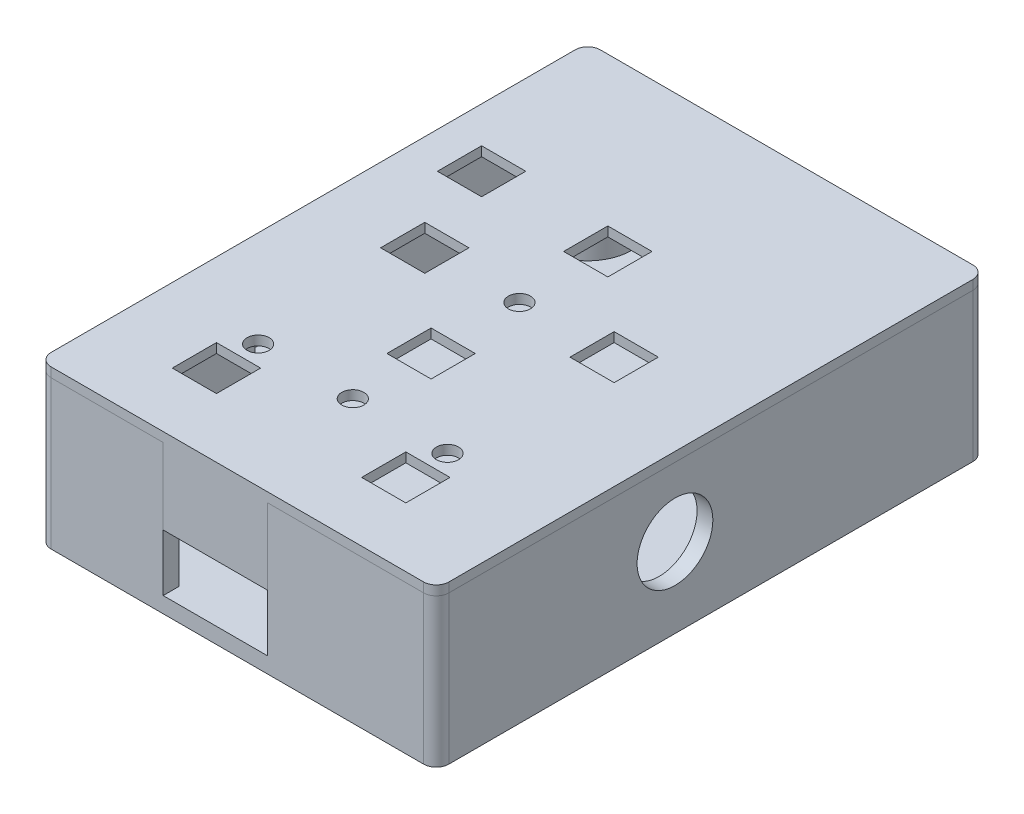
SolidWorks part; units mm, degrees
ref_plane "前视基准面" through (0, 0, 0) normal (0, 0, 1) x (1, 0, 0)
ref_plane "上视基准面" through (0, 0, 0) normal (0, 1, 0) x (1, 0, 0)
ref_plane "右视基准面" through (0, 0, 0) normal (1, 0, 0) x (0, 0, -1)
sketch "草图1" plane through (0, 0, 0) normal (0, 1, 0) x (1, 0, 0)
  line L0 (-11.76, -41) -> (-11.76, -43.5)
  line L1 (-26, 38) -> (26, 38) construction
  line L2 (-26, 38) -> (-26, -38) construction
  line L3 (-26, -38) -> (26, -38) construction
  line L4 (26, 38) -> (26, -38) construction
  line L5 (-26, 38) -> (26, -38) construction
  line L6 (-26, -38) -> (26, 38) construction
  line L7 (-29, 41) -> (29, 41)
  line L8 (-29, 41) -> (-29, -41)
  line L9 (-29, -41) -> (29, -41)
  line L10 (29, 41) -> (29, -41)
  line L11 (-29, 41) -> (29, -41) construction
  line L12 (-29, -41) -> (29, 41) construction
  line L13 (-29.5, 43.5) -> (29.5, 43.5)
  line L14 (-31.5, 41.5) -> (-31.5, -41.5)
  line L15 (-29.5, -43.5) -> (29.5, -43.5)
  line L16 (31.5, 41.5) -> (31.5, -41.5)
  line L17 (-31.5, 43.5) -> (31.5, -43.5) construction
  line L18 (-31.5, -43.5) -> (31.5, 43.5) construction
  line L19 (4.74, -41) -> (4.74, -43.5)
  line L20 (23.65, 43.5) -> (23.65, 41)
  line L21 (-23.35, 43.5) -> (-23.35, 41)
  line L22 (-16.35, 43.5) -> (-16.35, 41)
  line L23 (-31.5, 0.32) -> (-29, 0.32)
  line L24 (-31.5, -11.68) -> (-29, -11.68)
  circle A0 centre (-26, 38) radius 0.75
  circle A1 centre (26, 38) radius 0.75
  circle A2 centre (26, -38) radius 0.75
  circle A3 centre (-26, -38) radius 0.75
  arc A4 (-29.5, -43.5) -> (-31.5, -41.5) centre (-29.5, -41.5) cw
  arc A5 (31.5, -41.5) -> (29.5, -43.5) centre (29.5, -41.5) cw
  arc A6 (29.5, 43.5) -> (31.5, 41.5) centre (29.5, 41.5) cw
  arc A7 (-29.5, 43.5) -> (-31.5, 41.5) centre (-29.5, 41.5) ccw
  arc A8 (-29, -34) -> (-22, -41) centre (-29, -41) cw
  arc A9 (22, -41) -> (29, -34) centre (29, -41) cw
  arc A10 (29, 34) -> (22, 41) centre (29, 41) cw
  arc A11 (-22, 41) -> (-29, 34) centre (-29, 41) cw
  point P0 (0, 0)
  point P10 (0, 0)
  point P15 (0, 0)
  dimension "D3" = 1.5
  dimension "D8" = 2
  dimension "D11" = 7
  dimension "D1" = 76
  dimension "D2" = 52
  dimension "D4" = 3
  dimension "D5" = 3
  dimension "D6" = 2.5
  dimension "D7" = 2.5
  dimension "D9" = 14.24
  dimension "D10" = 16.5
  dimension "D12" = 2.35
  dimension "D13" = 7
  dimension "D14" = 40
  dimension "D15" = 12
  dimension "D16" = 26.32
extrude "凸台-拉伸1" add sketch "草图1" against normal blind 2.5 contours L14 A4 L15 A5 L16 A6 L13 A7
extrude "凸台-拉伸2" add sketch "草图1<4>" along normal blind 3 contours A11 L7 L8 A0 | A10 L10 L7 A1 | A9 L9 L10 A2 | A8 L8 L9 A3 region at (-25.5, 0, 40.901) region at (24.1203, 0, 36.1203) region at (24.1203, 0, -36.1203) region at (-28.901, 0, -37.5)
sketch "草图1<4>" plane through (0, 0, 0) normal (0, 1, 0) x (1, 0, 0) same geometry as "草图1"
extrude "凸台-拉伸4" add sketch "草图1<5>" along normal blind 4.6 separate body contours L13 L21 L7 L20 region at (3.65, 0, -42.25)
sketch "草图1<5>" plane through (0, 0, 0) normal (0, 1, 0) x (1, 0, 0) same geometry as "草图1"
extrude "凸台-拉伸5" add sketch "草图1<6>" along normal blind 21 contours L13 A7 L14 A4 L15 L0 L9 L8 L7 L21 | A6 L13 L20 L7 L10 L9 L19 L15 A5 L16 | L13 A7 L14 L23 L8 L7 L21 region at (-12.1345, 0, 42.25) region at (13.37, 0, 41.9102) region at (-29.7695, 0, -24.1304)
sketch "草图1<6>" plane through (0, 0, 0) normal (0, 1, 0) x (1, 0, 0) same geometry as "草图1"
extrude "凸台-拉伸6" add sketch "草图1<7>" along normal blind 9.4 contours L22 L13 L21 L7 region at (-19.85, 0, -42.25)
sketch "草图1<7>" plane through (0, 0, 0) normal (0, 1, 0) x (1, 0, 0) same geometry as "草图1"
sketch "草图2" plane through (0, 0, -43.5) normal (0, 0, -1) x (-1, 0, 0)
  line L0 (23.35, 9.4) -> (16.35, 9.4) construction
  circle A0 centre (19.85, 9.4) radius 3.5
extrude "切除-拉伸1" cut sketch "草图2" against normal up to next
sketch "草图3" plane through (31.5, 0, 0) normal (1, 0, 0) x (0, 0, -1)
  line L2 (-38, 3) -> (-38, 0) construction
  line L3 (34, 0) -> (-34, 0) construction
  circle A0 centre (-5.68, 10.1) radius 6
  dimension "D2" = 12
  dimension "D1" = 32.32
  dimension "D3" = 10.1
extrude "切除-拉伸2" cut sketch "草图3" against normal up to next
extrude "凸台-拉伸11" add sketch "草图1<8>" along normal blind 7 contours L14 L24 L8 L23 region at (-30.25, 0, 5.68)
sketch "草图1<8>" plane through (0, 0, 0) normal (0, 1, 0) x (1, 0, 0) same geometry as "草图1"
sketch "草图4" plane through (0, 21, 0) normal (0, 1, 0) x (1, 0, 0)
  line L0 (-11.76, -41) -> (-11.76, -43.5)
  line L1 (-26, 38) -> (26, 38) construction
  line L2 (-26, 38) -> (-26, -38) construction
  line L3 (-26, -38) -> (26, -38) construction
  line L4 (26, 38) -> (26, -38) construction
  line L5 (-26, 38) -> (26, -38) construction
  line L6 (-26, -38) -> (26, 38) construction
  line L7 (-29, 41) -> (29, 41)
  line L8 (-29, 41) -> (-29, -41)
  line L9 (-29, -41) -> (29, -41)
  line L10 (29, 41) -> (29, -41)
  line L11 (-29, 41) -> (29, -41) construction
  line L12 (-29, -41) -> (29, 41) construction
  line L13 (-29.5, 43.5) -> (29.5, 43.5)
  line L14 (-31.5, 41.5) -> (-31.5, -41.5)
  line L15 (-29.5, -43.5) -> (29.5, -43.5)
  line L16 (31.5, 41.5) -> (31.5, -41.5)
  line L17 (-31.5, 43.5) -> (31.5, -43.5) construction
  line L18 (-31.5, -43.5) -> (31.5, 43.5) construction
  line L19 (4.74, -41) -> (4.74, -43.5)
  line L20 (23.65, 43.5) -> (23.65, 41)
  line L21 (-23.35, 43.5) -> (-23.35, 41)
  line L22 (-16.35, 43.5) -> (-16.35, 41)
  line L23 (-31.5, 0.32) -> (-29, 0.32)
  line L24 (-31.5, -11.68) -> (-29, -11.68)
  line L25 (10.25, 5.93) -> (17.25, 5.93)
  line L26 (-16.35, 43.5) -> (-23.35, 43.5) construction
  line L27 (-11.76, -41) -> (-11.76, -43.5) construction
  line L28 (4.74, -41) -> (4.74, -43.5) construction
  line L29 (-29, -41) -> (-11.76, -41) construction
  line L30 (29, 41) -> (29, -41) construction
  line L31 (31.5, 41.5) -> (31.5, -41.5) construction
  line L32 (-23.35, 43.5) -> (-23.35, 41) construction
  line L33 (-16.35, 43.5) -> (-16.35, 41) construction
  line L34 (23.65, 43.5) -> (23.65, 41) construction
  line L35 (-4.75, 19.93) -> (2.25, 19.93)
  line L36 (-4.75, 19.93) -> (-4.75, 12.93)
  line L37 (-4.75, 12.93) -> (2.25, 12.93)
  line L38 (2.25, 19.93) -> (2.25, 12.93)
  line L39 (-4.75, 19.93) -> (2.25, 12.93) construction
  line L40 (-4.75, 12.93) -> (2.25, 19.93) construction
  line L41 (10.25, 5.93) -> (10.25, -1.07)
  line L42 (10.25, -1.07) -> (17.25, -1.07)
  line L43 (17.25, 5.93) -> (17.25, -1.07)
  line L44 (10.25, 5.93) -> (17.25, -1.07) construction
  line L45 (10.25, -1.07) -> (17.25, 5.93) construction
  line L46 (-19.75, 5.93) -> (-12.75, 5.93)
  line L47 (-19.75, 5.93) -> (-19.75, -1.07)
  line L48 (-19.75, -1.07) -> (-12.75, -1.07)
  line L49 (-12.75, 5.93) -> (-12.75, -1.07)
  line L50 (-19.75, 5.93) -> (-12.75, -1.07) construction
  line L51 (-19.75, -1.07) -> (-12.75, 5.93) construction
  line L52 (-4.75, -8.07) -> (2.25, -8.07)
  line L53 (-4.75, -8.07) -> (-4.75, -15.07)
  line L54 (-4.75, -15.07) -> (2.25, -15.07)
  line L55 (2.25, -8.07) -> (2.25, -15.07)
  line L56 (-4.75, -8.07) -> (2.25, -15.07) construction
  line L57 (-4.75, -15.07) -> (2.25, -8.07) construction
  line L58 (-19.75, -27.07) -> (-12.75, -27.07)
  line L59 (-19.75, -27.07) -> (-19.75, -34.07)
  line L60 (-19.75, -34.07) -> (-12.75, -34.07)
  line L61 (-12.75, -27.07) -> (-12.75, -34.07)
  line L62 (-19.75, -27.07) -> (-12.75, -34.07) construction
  line L63 (-19.75, -34.07) -> (-12.75, -27.07) construction
  line L64 (10.25, -27.07) -> (17.25, -27.07)
  line L65 (10.25, -27.07) -> (10.25, -34.07)
  line L66 (10.25, -34.07) -> (17.25, -34.07)
  line L67 (17.25, -27.07) -> (17.25, -34.07)
  line L68 (10.25, -27.07) -> (17.25, -34.07) construction
  line L69 (10.25, -34.07) -> (17.25, -27.07) construction
  line L70 (-16.25, 2.43) -> (13.75, 2.43) construction
  line L71 (-1.25, 2.43) -> (-1.25, 16.43) construction
  line L72 (-16.25, -30.57) -> (13.75, -30.57) construction
  line L73 (-1.25, -30.57) -> (-1.25, -11.57) construction
  line L74 (-1.25, 2.43) -> (-1.25, -11.57) construction
  line L75 (-16.25, -23.97) -> (-16.25, -30.57) construction
  line L76 (13.75, -23.97) -> (13.75, -30.57) construction
  line L77 (-16.25, -23.97) -> (13.75, -23.97) construction
  line L78 (-25.75, 20.93) -> (-18.75, 20.93)
  line L79 (-25.75, 20.93) -> (-25.75, 13.93)
  line L80 (-25.75, 13.93) -> (-18.75, 13.93)
  line L81 (-18.75, 20.93) -> (-18.75, 13.93)
  line L82 (-25.75, 20.93) -> (-18.75, 13.93) construction
  line L83 (-25.75, 13.93) -> (-18.75, 20.93) construction
  circle A0 centre (-26, 38) radius 0.75
  circle A1 centre (26, 38) radius 0.75
  circle A2 centre (26, -38) radius 0.75
  circle A3 centre (-26, -38) radius 0.75
  arc A4 (-29.5, -43.5) -> (-31.5, -41.5) centre (-29.5, -41.5) cw
  arc A5 (31.5, -41.5) -> (29.5, -43.5) centre (29.5, -41.5) cw
  arc A6 (29.5, 43.5) -> (31.5, 41.5) centre (29.5, 41.5) cw
  arc A7 (-29.5, 43.5) -> (-31.5, 41.5) centre (-29.5, 41.5) ccw
  arc A8 (-29, -34) -> (-22, -41) centre (-29, -41) cw
  arc A9 (22, -41) -> (29, -34) centre (29, -41) cw
  arc A10 (29, 34) -> (22, 41) centre (29, 41) cw
  arc A11 (-22, 41) -> (-29, 34) centre (-29, 41) cw
  circle A12 centre (-26, 38) radius 0.75 construction
  arc A13 (-29, 34) -> (-22, 41) centre (-29, 41) ccw construction
  arc A14 (-29.5, 43.5) -> (-31.5, 41.5) centre (-29.5, 41.5) ccw construction
  circle A15 centre (-1.25, 2.43) radius 1.75
  circle A16 centre (-16.25, -23.97) radius 1.75
  circle A17 centre (-1.25, -23.97) radius 1.75
  circle A18 centre (13.75, -23.97) radius 1.75
  point P0 (0, 0)
  point P9 (0, 0)
  point P14 (0, 0)
  point P85 (-1.25, 16.43)
  point P90 (13.75, 2.43)
  point P95 (-16.25, 2.43)
  point P100 (-1.25, -11.57)
  point P105 (-16.25, -30.57)
  point P110 (13.75, -30.57)
  point P130 (-22.25, 17.43)
  line M14 (-31.5, -11.68) -> (-31.5, -41.5)
  arc M15 (-31.5, -41.5) -> (-29.5, -43.5) centre (-29.5, -41.5) ccw
  line M16 (-29.5, -43.5) -> (-11.76, -43.5)
  line M17 (-11.76, -43.5) -> (-11.76, -41)
  line M18 (-11.76, -41) -> (-29, -41)
  line M19 (-29, -41) -> (-29, -11.68)
  line M58 (-29, -11.68) -> (-31.5, -11.68)
  dimension "D4" = 3.5
  dimension "D1" = 7
  dimension "D2" = 30
  dimension "D3" = 14
  dimension "D5" = 19
  dimension "D6" = 7.43
  dimension "D7" = 6.6
  dimension "D8" = 15
  dimension "D9" = 6
  dimension "D10" = 24.75
extrude "凸台-拉伸7" add sketch "草图4" along normal blind 1.5 separate body contours L7 A11 L8 A8 L9 A9 L10 A10 A18 A17 A16 A15 L35 L38 L37 L36 L25 L43 L42 L41 L46 L49 L48 L47 L52 L55 L54 L53 L58 L61 L60 L59 L64 L67 L66 L65 M18 | L23 L14 L8 M58 | L13 A7 L14 L23 L8 L7 L21 | L9 L8 M14 M15 M16 M17 M18 M19 M58 | A8 L9 A3 M19 | L19 L9 L15 M17 | A6 L13 L20 L7 L10 L9 L19 L15 A5 L16 | A9 L9 L10 A2 | A10 L10 L7 A1 | L13 L22 L7 L20 | A11 L7 L8 A0 | L22 L13 L21 L7 | A0 | A1 | A2 | A3 region at (-3.51, 21, 42.25) region at (-12.1345, 21, 42.25) region at (0.3568, 21, -0.553) region at (-25.5, 21, 40.901) region at (13.37, 21, 41.9102) region at (24.1203, 21, 36.1203) region at (-30.25, 21, 5.68) region at (-29.7695, 21, -24.1304) region at (24.1203, 21, -36.1203) region at (-28.901, 21, -37.5) region at (3.65, 21, -42.25) region at (-19.85, 21, -42.25) region at (-26, 21, -38) region at (26, 21, -38) region at (26, 21, 38) region at (-26, 21, 38)
extrude "凸台-拉伸8" add sketch "草图4<4>" against normal blind 12 contours L19 L9 L15 M17 region at (-3.51, 21, 42.25)
sketch "草图4<4>" plane through (0, 21, 0) normal (0, 1, 0) x (1, 0, 0) same geometry as "草图4"
extrude "凸台-拉伸9" add sketch "草图4<5>" against normal blind 11.5 contours L22 L13 L7 region at (-19.85, 21, -42.25)
sketch "草图4<5>" plane through (0, 21, 0) normal (0, 1, 0) x (1, 0, 0) same geometry as "草图4"
sketch "草图5" plane through (0, 0, -43.5) normal (0, 0, -1) x (-1, 0, 0)
  line L0 (23.35, 9.5) -> (16.35, 9.5) construction
  circle A0 centre (19.85, 9.5) radius 3.5
  dimension "D1" = 7
extrude "切除-拉伸3" cut sketch "草图5" against normal up to next (2.5 mm away)
extrude "凸台-拉伸10" add sketch "草图4<6>" against normal blind 4.4 contours L13 L22 L7 L20 region at (3.65, 21, -42.25)
sketch "草图4<6>" plane through (0, 21, 0) normal (0, 1, 0) x (1, 0, 0) same geometry as "草图4"
extrude "凸台-拉伸12" add sketch "草图4<7>" against normal blind 8.6 contours L23 L14 L8 M58 region at (-30.25, 21, 5.68)
sketch "草图4<7>" plane through (0, 21, 0) normal (0, 1, 0) x (1, 0, 0) same geometry as "草图4"
